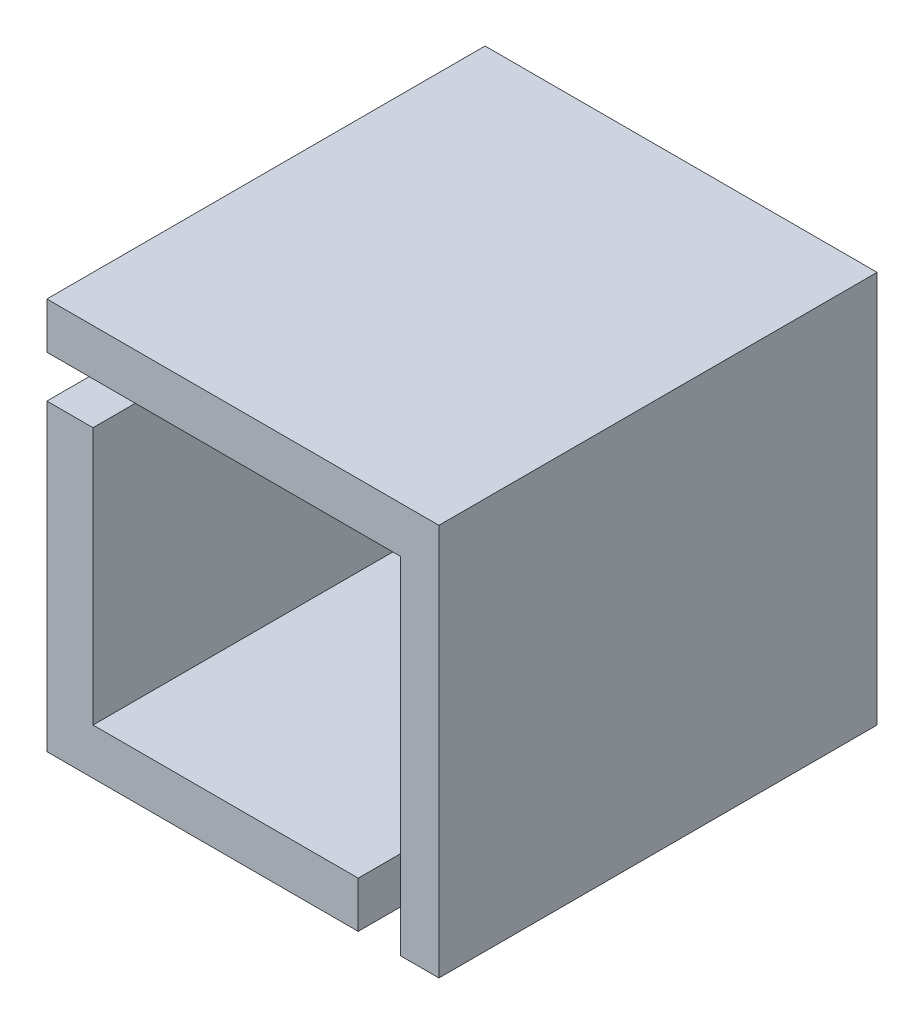
SolidWorks part; units mm, degrees
ref_plane "Front Plane" through (0, 0, 0) normal (0, 0, 1) x (1, 0, 0)
ref_plane "Top Plane" through (0, 0, 0) normal (0, 1, 0) x (1, 0, 0)
ref_plane "Right Plane" through (0, 0, 0) normal (1, 0, 0) x (0, 0, -1)
sketch "Sketch1" plane through (0, 0, 0) normal (0, 0, 1) x (1, 0, 0)
  line L0 (-31.7401, 10.2517) -> (-6.2401, 10.2517)
  line L1 (-6.2401, 10.2517) -> (-6.2401, -15.2483)
  line L2 (-6.2401, -15.2483) -> (-31.7401, -15.2483)
  line L3 (-31.7401, -15.2483) -> (-31.7401, 10.2517)
  dimension "D1" = 25.5
  dimension "D2" = 25.5
extrude "Boss-Extrude5" add sketch "Sketch1" along normal blind 3
sketch "Sketch2" plane through (0, 0, 3) normal (0, 0, 1) x (1, 0, 0)
  line L0 (-31.7401, 10.2517) -> (-6.2401, 10.2517)
  line L1 (-6.2401, 10.2517) -> (-31.7401, 10.2517) construction
  line L2 (-6.2401, 10.2517) -> (-6.2401, -15.2483)
  line L3 (-6.2401, -15.2483) -> (-6.2401, 10.2517) construction
  line L4 (-6.2401, -15.2483) -> (-8.7401, -15.2483)
  line L5 (-31.7401, -15.2483) -> (-6.2401, -15.2483) construction
  line L6 (-8.7401, -15.2483) -> (-8.7401, 7.2517)
  line L7 (-8.7401, 7.2517) -> (-31.7401, 7.2517)
  line L8 (-31.7401, 10.2517) -> (-31.7401, -15.2483) construction
  line L9 (-31.7401, 7.2517) -> (-31.7401, 10.2517)
  line L10 (-31.7401, 4.5017) -> (-28.7401, 4.5017)
  line L11 (-28.7401, 4.5017) -> (-28.7401, -12.2483)
  line L12 (-28.7401, -12.2483) -> (-11.4901, -12.2483)
  line L13 (-11.4901, -12.2483) -> (-11.4901, -15.2483)
  line L14 (-11.4901, -15.2483) -> (-31.7401, -15.2483)
  line L15 (-31.7401, -15.2483) -> (-31.7401, 4.5017)
  point P18 (-6.2401, -15.2483)
  dimension "D1" = 2.75
  dimension "D2" = 3
  dimension "D3" = 3
  dimension "D4" = 3
  dimension "D6" = 2.75
  dimension "D7" = 23
  dimension "D8" = 22.5
extrude "Boss-Extrude6" add sketch "Sketch2" along normal blind 25.5
